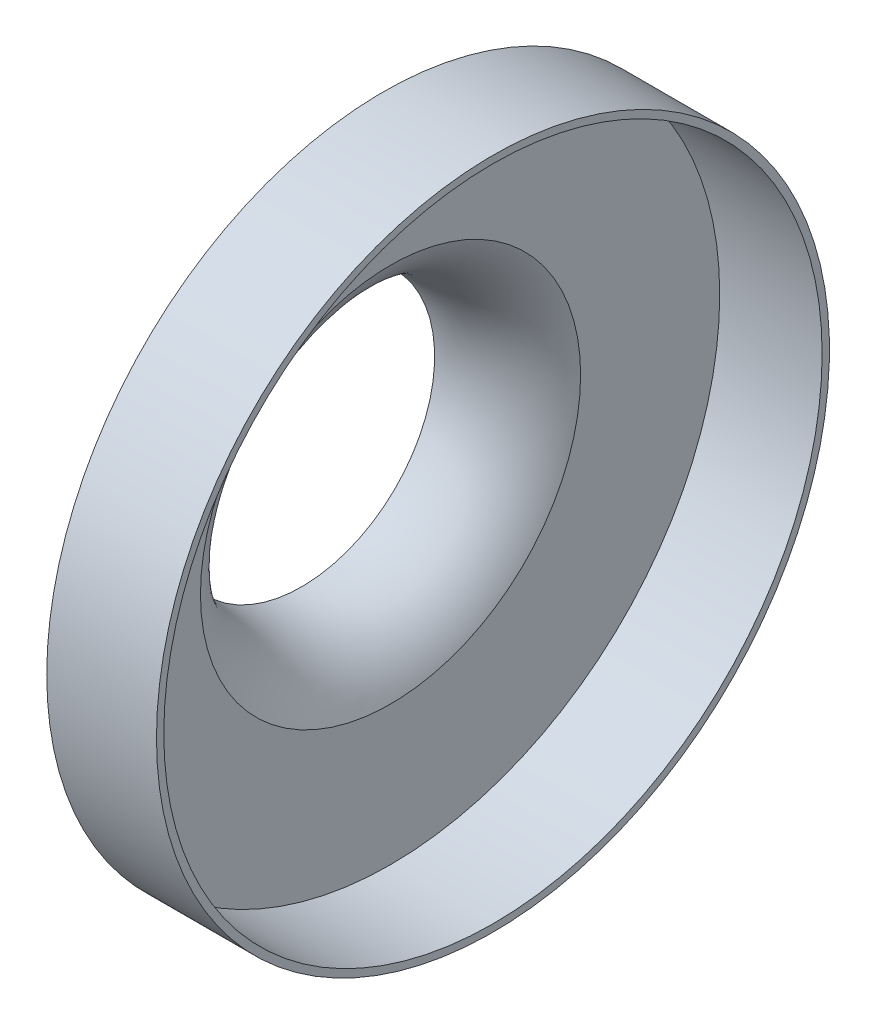
SolidWorks part; units mm, degrees
ref_plane "Front Plane" through (0, 0, 0) normal (0, 0, 1) x (1, 0, 0)
ref_plane "Top Plane" through (0, 0, 0) normal (0, 1, 0) x (1, 0, 0)
ref_plane "Right Plane" through (0, 0, 0) normal (1, 0, 0) x (0, 0, -1)
sketch "Sketch1" plane through (0, 0, 0) normal (0, 0, 1) x (1, 0, 0)
  line L0 (15.4464, 33.0001) -> (15.4464, 57.15)
  line L1 (0, 33.0001) -> (24.7431, 33.0001) construction
  line L2 (15.4464, 57.15) -> (33.2264, 57.15)
  line L3 (0, 0) -> (54.525, 0) construction
  line L4 (14.1764, 33.2836) -> (14.1764, 58.42)
  line L5 (14.1764, 58.42) -> (33.2264, 58.42)
  line L6 (33.2264, 58.42) -> (33.2264, 57.15)
  line L7 (0, 24.37) -> (0, 23.1)
  circle A0 centre (0, 40.1) radius 17 construction
  arc A1 (0, 23.1) -> (15.4464, 33.0001) centre (0, 40.1) ccw
  arc A2 (0, 24.37) -> (14.1764, 33.2836) centre (0, 40.1) ccw
  point P0 (0, 23.1)
  dimension "D3" = 17
  dimension "D1" = 33.0001
  dimension "D2" = 23.1
  dimension "D4" = 33.9999
  dimension "D5" = 57.15
  dimension "D6" = 17.78
  dimension "D7" = 1.27
revolve "Revolve1" add sketch "Sketch1" angle 360 about L3
